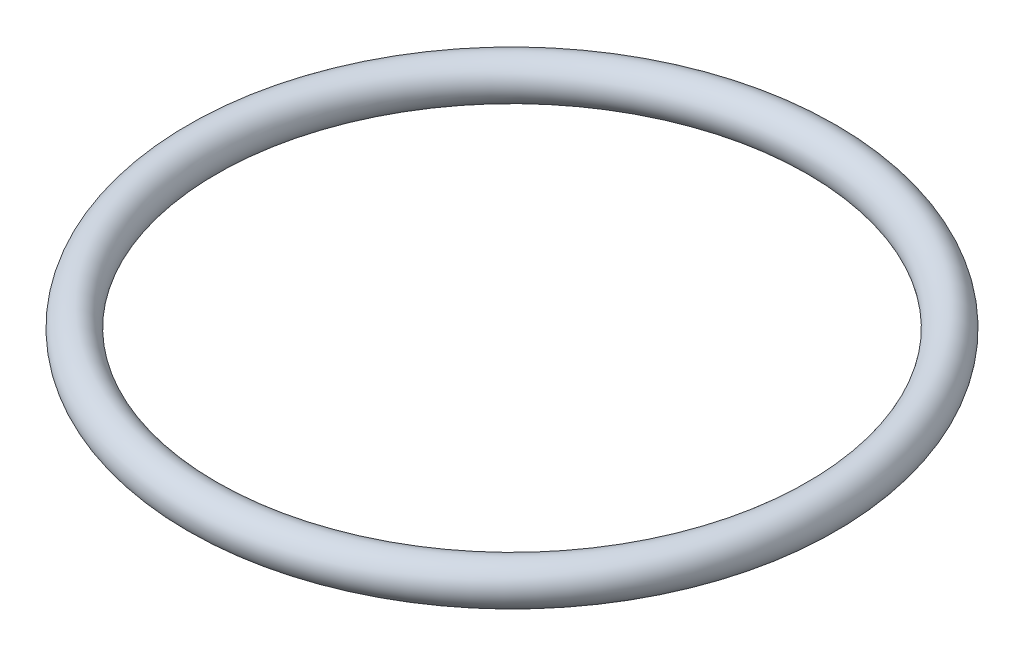
SolidWorks part; units mm, degrees
ref_plane "Front Plane" through (0, 0, 0) normal (0, 0, 1) x (1, 0, 0)
ref_plane "Top Plane" through (0, 0, 0) normal (0, 1, 0) x (1, 0, 0)
ref_plane "Right Plane" through (0, 0, 0) normal (1, 0, 0) x (0, 0, -1)
sketch "Sketch1" plane through (0, 0, 0) normal (0, 1, 0) x (1, 0, 0)
  circle A1 centre (0, 0) radius 18.8849
  dimension "B" = 37.7698
sketch "Sketch2" plane through (0, 0, 0) normal (0, 0, 1) x (1, 0, 0)
  circle A0 centre (-20.193, 0) radius 1.3081
  point P4 (-18.8849, 0)
  dimension "A" = 2.6162
sweep "Sweep1" add profiles "Sketch2" path "Sketch1"
ref_axis "Axis1" through (0, 5.2562, 0) along (0, -1, 0)
